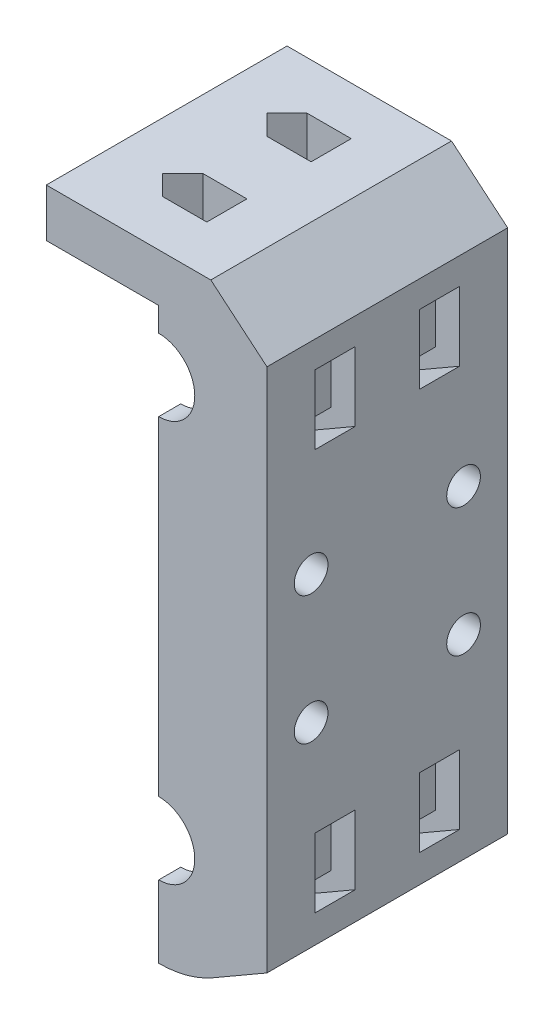
SolidWorks part; units mm, degrees
material "Printed PLA"
ref_plane "Front Plane" through (0, 0, 0) normal (0, 0, 1) x (1, 0, 0)
ref_plane "Top Plane" through (0, 0, 0) normal (0, 1, 0) x (1, 0, 0)
ref_plane "Right Plane" through (0, 0, 0) normal (1, 0, 0) x (0, 0, -1)
sketch "Sketch1" plane through (0, 0, 0) normal (0, 0, 1) x (1, 0, 0)
  line L0 (0, -25) -> (0, 25) construction
  line L1 (13.5, -25) -> (13.5, 25)
  line L2 (0, 38.5) -> (0, 32.5)
  line L3 (0, -38.5) -> (0, -32.5)
  line L4 (0, -17.5) -> (0, 17.5)
  line L5 (13.5, -25) -> (13.5, -32.7942)
  line L6 (13.5, -38.5) -> (0, -38.5) construction
  line L7 (6.75, 36.6913) -> (13.5, 32.7942)
  line L8 (13.5, 32.7942) -> (13.5, 25)
  line L9 (6.75, -36.6913) -> (13.5, -32.7942)
  arc A0 (0, 17.5) -> (0, 32.5) centre (0, 25) ccw
  arc A1 (0, -32.5) -> (0, -17.5) centre (0, -25) ccw
  arc A2 (6.75, 36.6913) -> (0, 38.5) centre (0, 25) ccw
  arc A3 (13.5, -25) -> (0, -38.5) centre (0, -25) cw construction
  arc A4 (6.75, 36.6913) -> (13.5, 25) centre (0, 25) cw construction
  arc A5 (6.75, -36.6913) -> (0, -38.5) centre (0, -25) cw
  dimension "D2" = 15
  dimension "D1" = 50
  dimension "D3" = 6
  dimension "D4" = 60
extrude "Boss-Extrude1" add sketch "Sketch1" along normal mid plane 30
sketch "Sketch2" plane through (0, 0, 15) normal (0, 0, 1) x (1, 0, 0)
  line L0 (0, 32.5) -> (0, 29.5)
  line L1 (0, 20.5) -> (0, 17.5)
  line L2 (0, -17.5) -> (0, -20.5)
  line L3 (0, -29.5) -> (0, -32.5)
  arc A0 (0, 29.5) -> (0, 20.5) centre (0, 25) cw
  arc A1 (0, 17.5) -> (0, 32.5) centre (0, 25) ccw
  arc A2 (0, -20.5) -> (0, -29.5) centre (0, -25) cw
  arc A3 (0, -32.5) -> (0, -17.5) centre (0, -25) ccw
  dimension "D1" = 4.5
extrude "Boss-Extrude2" add sketch "Sketch2" against normal blind 2.75
mirror "Mirror1" about plane through (0, 0, 0) normal (0, 0, 1) of "Boss-Extrude2"
sketch "Sketch3" plane through (0, 0, 15) normal (0, 0, 1) x (1, 0, 0)
  line L0 (0, 34.5) -> (0, 36.5)
  line L1 (0, 38.5) -> (0, 29.5) construction
  line L2 (1.951, 35.9772) -> (13.5, 29.3094)
  line L3 (13.5, -32.7942) -> (13.5, 32.7942) construction
  line L4 (13.5, 29.3094) -> (13.5, 27)
  line L5 (13.5, 27) -> (0.951, 34.2452)
  line L6 (13.5, 32.7942) -> (6.75, 36.6913) construction
  line L7 (0, 25) -> (4.5, 25) construction
  line L8 (13.5, 23) -> (0.951, 15.7548)
  line L9 (13.5, 20.6906) -> (13.5, 23)
  line L10 (1.951, 14.0228) -> (13.5, 20.6906)
  line L11 (0, 15.5) -> (0, 13.5)
  arc A1 (0, 36.5) -> (1.951, 35.9772) centre (0, 32.5981) cw
  arc A2 (0.951, 34.2452) -> (0, 34.5) centre (0, 32.5981) ccw
  arc A4 (0, 20.5) -> (0, 29.5) centre (0, 25) ccw construction
  arc A5 (0.951, 15.7548) -> (0, 15.5) centre (0, 17.4019) cw
  arc A6 (0, 13.5) -> (1.951, 14.0228) centre (0, 17.4019) ccw
  dimension "D1" = 2
  dimension "D2" = 2
  dimension "D3" = 4
extrude "Cut-Extrude1" cut sketch "Sketch3" against normal blind 5 from offset 6 offset against normal yes
sketch "Sketch5" plane through (13.5, 0, 0) normal (1, 0, 0) x (0, 0, -1)
  line L1 (-9, 29.3094) -> (-4, 29.3094)
  line L2 (-9, 29.3094) -> (-9, 20.6906)
  line L3 (-9, 20.6906) -> (-4, 20.6906)
  line L4 (-4, 29.3094) -> (-4, 20.6906)
extrude "Cut-Extrude2" cut sketch "Sketch5" against normal blind 3
mirror "Mirror3" about plane through (0, 0, 0) normal (0, 0, 1) of "Cut-Extrude2", "Cut-Extrude1"
mirror "Mirror5" about plane through (0, 0, 0) normal (0, 1, 0) of "Mirror3"
sketch "Sketch6" plane through (13.5, 0, 0) normal (1, 0, 0) x (0, 0, -1)
  line L0 (-9.5, -8.5) -> (9.5, -8.5) construction
  line L1 (0, -8.5) -> (0, 0) construction
  line L2 (0, 7.5) -> (0, 0) construction
  circle A0 centre (-9.5, -8.5) radius 2.1
  circle A1 centre (9.5, -8.5) radius 2.1
  circle A2 centre (0, 7.5) radius 2.1 construction
  dimension "D2" = 4.2
  dimension "D1" = 19
  dimension "D3" = 8.5
  dimension "D4" = 16
extrude "Cut-Extrude3" cut sketch "Sketch6" against normal through all
sketch "Sketch7" plane through (0, 0, 0) normal (-1, 0, 0) x (0, 0, 1)
  circle A0 centre (-9.5, -8.5) radius 4
  circle A1 centre (9.5, -8.5) radius 4
  dimension "D1" = 8
extrude "Cut-Extrude4" [suppressed] cut sketch "Sketch7" against normal blind 3
pattern_linear "LPattern2" count 2 spacing 16 along (0, 1, 0) of "Cut-Extrude3", "Cut-Extrude4"
sketch "Sketch8" plane through (0, 0, 15) normal (0, 0, 1) x (1, 0, 0)
  line L0 (0, 38.5) -> (13.5, 38.5)
  line L1 (13.5, 38.5) -> (13.5, 32.7942)
  line L2 (13.5, 32.7942) -> (6.75, 36.6913)
  arc A0 (6.75, 36.6913) -> (0, 38.5) centre (0, 25) ccw
extrude "Boss-Extrude3" add sketch "Sketch8" against normal up to surface (30 mm away) up to face at (4.9738, 0, -15)
sketch "Sketch9" plane through (0, 0, 0) normal (-1, 0, 0) x (0, 0, 1)
  line L0 (15, 38.5) -> (-15, 38.5) construction
  line L1 (-4, 38.5) -> (4, 38.5)
  line L2 (-4, 38.5) -> (-4, 32.5)
  line L3 (-4, 32.5) -> (4, 32.5)
  line L4 (4, 38.5) -> (4, 32.5)
  line L5 (12.25, 32.5) -> (-12.25, 32.5) construction
  line L6 (4, 36.5) -> (4, 34.5) construction
  line L7 (-9, 36.5) -> (-9, 34.5) construction
  line L8 (-4, 36.5) -> (-4, 34.5) construction
  line L9 (15, 38.5) -> (15, 29.5) construction
  line L10 (9, 38.5) -> (15, 38.5)
  line L11 (9, 38.5) -> (9, 32.5)
  line L12 (9, 32.5) -> (15, 32.5)
  line L13 (15, 38.5) -> (15, 32.5)
  line L14 (-15, 38.5) -> (-15, 29.5) construction
  line L15 (-9, 38.5) -> (-15, 38.5)
  line L16 (-9, 38.5) -> (-9, 32.5)
  line L17 (-9, 32.5) -> (-15, 32.5)
  line L18 (-15, 38.5) -> (-15, 32.5)
extrude "Boss-Extrude4" add sketch "Sketch9" along normal blind 14
sketch "Sketch10" plane through (-14, 0, 0) normal (-1, 0, 0) x (0, 0, 1)
  line L1 (-15, 38.5) -> (15, 38.5)
  line L2 (-15, 38.5) -> (-15, 32.5)
  line L3 (-15, 32.5) -> (15, 32.5)
  line L4 (15, 38.5) -> (15, 32.5)
extrude "Boss-Extrude5" add sketch "Sketch10" against normal blind 6
chamfer "Chamfer1" distance 2.5 angle 45 4 edges at (-8, 35.5, 4) (-8, 35.5, 9) (-8, 35.5, -4) (-8, 35.5, -9)
chamfer "Chamfer2" distance 7 angle 40 1 edges at (13.5, 38.5, 0) first distance on face at (-3.8, 38.5, 6.5)
